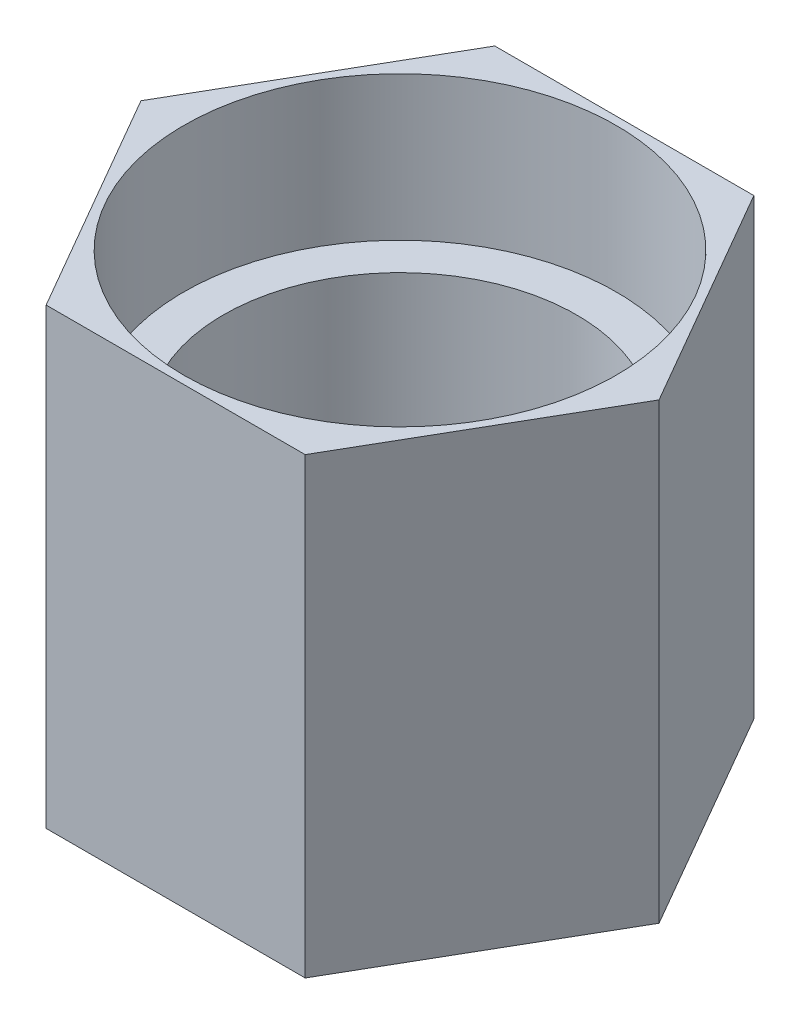
SolidWorks part; units mm, degrees
ref_plane "Front Plane" through (0, 0, 0) normal (0, 0, 1) x (1, 0, 0)
ref_plane "Top Plane" through (0, 0, 0) normal (0, 1, 0) x (1, 0, 0)
ref_plane "Right Plane" through (0, 0, 0) normal (1, 0, 0) x (0, 0, -1)
sketch "Sketch1" plane through (0, 0, 0) normal (0, 1, 0) x (1, 0, 0)
  line L1 (-3.5929, 6.223) -> (-7.1857, 0)
  line L2 (-7.1857, 0) -> (-3.5929, -6.223)
  line L3 (-3.5929, -6.223) -> (3.5929, -6.223)
  line L4 (3.5929, -6.223) -> (7.1857, 0)
  line L5 (7.1857, 0) -> (3.5929, 6.223)
  line L6 (3.5929, 6.223) -> (-3.5929, 6.223)
  circle A0 centre (0, 0) radius 6.223 construction
  circle A1 centre (0, 0) radius 6
  dimension "D1" = 12.446
  dimension "D2" = 12
extrude "Boss-Extrude1" add sketch "Sketch1" along normal blind 6.2865 and the other way blind 6.2865
sketch "Sketch2" plane through (0, 0, 0) normal (0, 1, 0) x (1, 0, 0)
  circle A0 centre (0, 0) radius 6 construction
  circle A1 centre (0, 0) radius 6
  circle A2 centre (0, 0) radius 4.9
  dimension "D1" = 9.8
extrude "Boss-Extrude2" add sketch "Sketch2" along normal blind 2.2865 and the other way blind 2.2865
